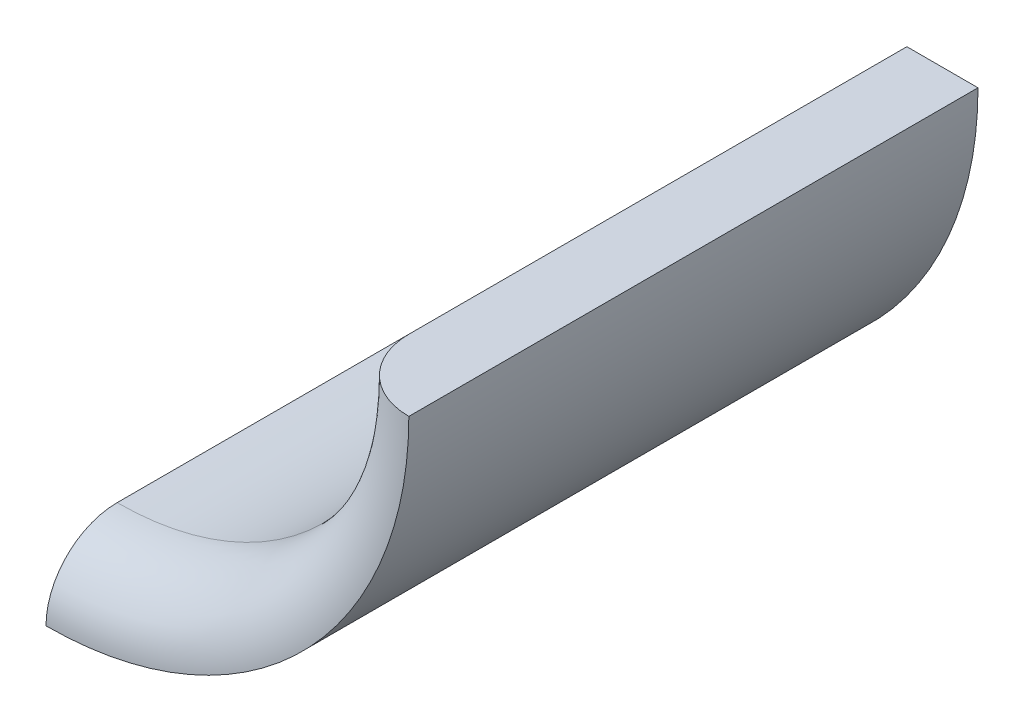
SolidWorks part; units mm, degrees
ref_plane "前视基准面" through (0, 0, 0) normal (0, 0, 1) x (1, 0, 0)
ref_plane "上视基准面" through (0, 0, 0) normal (0, 1, 0) x (1, 0, 0)
ref_plane "右视基准面" through (0, 0, 0) normal (1, 0, 0) x (0, 0, -1)
sketch "草图1" plane through (0, 0, 0) normal (0, 0, 1) x (1, 0, 0)
  circle A0 centre (0, 0) radius 410
  circle A1 centre (0, 0) radius 510
  dimension "D1" = 820
  dimension "D2" = 100
extrude "凸台-拉伸1" add sketch "草图1" along normal blind 800
fillet "圆角1" radius 100 1 edges at (410, 0, 800)
sketch "草图2" plane through (0, 0, 0) normal (0, 0, 1) x (1, 0, 0)
  line L1 (0, 764.1837) -> (-976.3611, 764.1837)
  line L2 (-976.3611, 764.1837) -> (-976.3611, 0)
  line L4 (0, 0) -> (0, -891.8351)
  line L5 (0, -891.8351) -> (-976.3611, -891.8351)
  line L6 (-976.3611, -891.8351) -> (-976.3611, 0)
  line L7 (0, 0) -> (1031.5617, 0)
  line L8 (1031.5617, 0) -> (1031.5617, 764.1837)
  line L9 (1031.5617, 764.1837) -> (0, 764.1837)
extrude "切除-拉伸2" cut sketch "草图2" along normal blind 800
